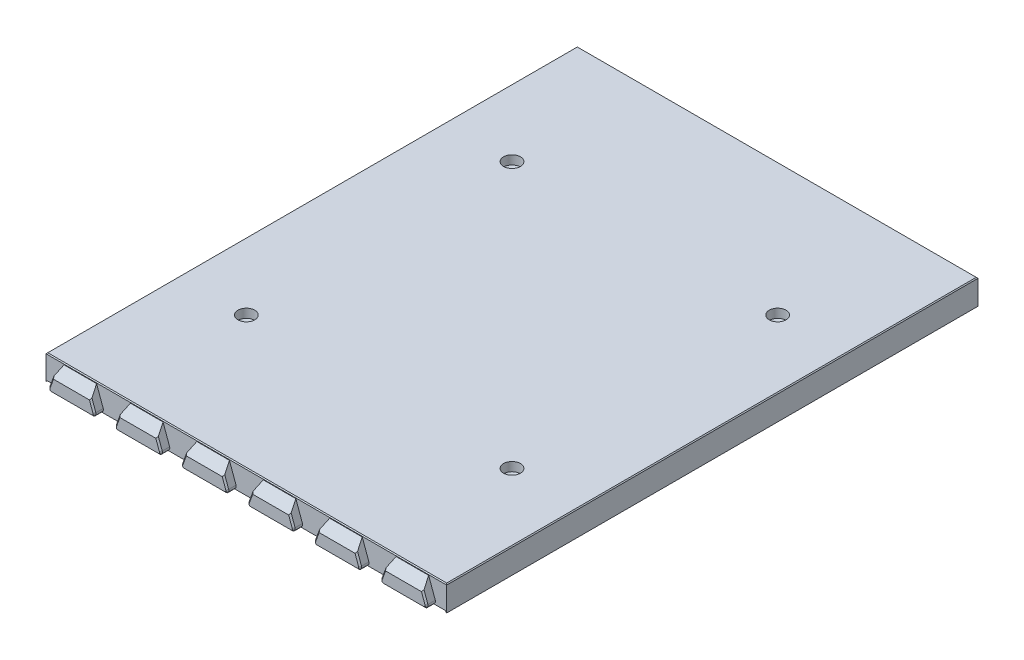
SolidWorks part; units mm, degrees
ref_plane "Front Plane" through (0, 0, 0) normal (0, 0, 1) x (1, 0, 0)
ref_plane "Top Plane" through (0, 0, 0) normal (0, 1, 0) x (1, 0, 0)
ref_plane "Right Plane" through (0, 0, 0) normal (1, 0, 0) x (0, 0, -1)
sketch "Sketch1" plane through (0, 0, 0) normal (0, 0, 1) x (1, 0, 0)
  line L0 (0, 0) -> (0, 8) construction
  line L1 (-67.875, 0) -> (0, 0) construction
  line L2 (-67.875, 0) -> (-67.875, 8)
  line L3 (-67.875, 8) -> (67.875, 8)
  line L5 (-67.875, 0) -> (-65.875, 0)
  line L6 (-65.875, 0) -> (-65.875, 6)
  line L7 (-65.875, 6) -> (65.875, 6)
  line L9 (65.875, 0) -> (65.875, 6)
  line L10 (67.875, 0) -> (65.875, 0)
  line L11 (67.875, 0) -> (67.875, 8)
  point P8 (0, 6)
  dimension "D2" = 6
  dimension "D1" = 67.875
  dimension "D3" = 2
  dimension "D4" = 2
extrude "Boss-Extrude1" add sketch "Sketch1" against normal blind 90
sketch "Sketch7" plane through (0, 0, 0) normal (0, 0, 1) x (1, 0, 0)
  line L2 (-65.875, 0) -> (65.875, 0)
  line L13 (-65.875, 0) -> (-65.875, 6)
  line L15 (-65.875, 6) -> (65.875, 6)
  line L16 (65.875, 0) -> (65.875, 6)
  line M3 (-65.875, 0) -> (-65.875, 6)
  line M4 (-65.875, 6) -> (65.875, 6)
  line M5 (65.875, 6) -> (65.875, 0)
extrude "Boss-Extrude7" add sketch "Sketch7" against normal blind 1 contours M4 M3 | M5 region at (0, 3, 0)
sketch "Sketch2" plane through (0, 0, 0) normal (0, 0, 1) x (1, 0, 0)
  line L14 (50.9118, 8) -> (48, 0)
  line L15 (67.875, 8) -> (-67.875, 8) construction
  line L16 (-67.875, 0) -> (67.875, 0) construction
  line L17 (48, 0) -> (64.5, 0)
  line L18 (50.9118, 8) -> (61.5882, 8)
  line L19 (-67.875, 0) -> (67.875, 0) construction
  line L21 (61.5882, 8) -> (64.5, 0)
  line L24 (45, 0) -> (45, 8) construction
  line L27 (28.4118, 8) -> (25.5, 0)
  line L28 (28.4118, 8) -> (39.0882, 8)
  line L29 (25.5, 0) -> (42, 0)
  line L30 (39.0882, 8) -> (42, 0)
  line L31 (5.9118, 8) -> (3, 0)
  line L32 (5.9118, 8) -> (16.5882, 8)
  line L33 (3, 0) -> (19.5, 0)
  line L34 (16.5882, 8) -> (19.5, 0)
  line L35 (-16.5882, 8) -> (-19.5, 0)
  line L36 (-16.5882, 8) -> (-5.9118, 8)
  line L37 (-19.5, 0) -> (-3, 0)
  line L38 (-5.9118, 8) -> (-3, 0)
  line L39 (50.9118, 8) -> (28.4118, 8) construction
  line L40 (67.5, 8) -> (67.5, 0) construction
  line L41 (67.875, 0) -> (67.875, 8) construction
  line L42 (-67.5, 8) -> (-67.5, 0) construction
  line L43 (-67.875, 8) -> (-67.875, 0) construction
  line L44 (-39.0882, 8) -> (-42, 0)
  line L45 (-39.0882, 8) -> (-28.4118, 8)
  line L46 (-42, 0) -> (-25.5, 0)
  line L47 (-28.4118, 8) -> (-25.5, 0)
  line L48 (-61.5882, 8) -> (-64.5, 0)
  line L49 (-61.5882, 8) -> (-50.9118, 8)
  line L50 (-64.5, 0) -> (-48, 0)
  line L51 (-50.9118, 8) -> (-48, 0)
  point P22 (56.25, 8)
  point P23 (33.75, 8)
  dimension "D1" = 70
  dimension "D2" = 0.375
  dimension "D3" = 3
  dimension "D4" = 3
  dimension "D5" = 70
  dimension "D7" = 22.5
  dimension "D8" = 22.5
  dimension "D9" = 0.375
  dimension "D10" = 48
  dimension "D11" = 8
  dimension "D6" = 6
extrude "Boss-Extrude4" add sketch "Sketch2" along normal blind 3
sketch "Sketch8" plane through (0, 0, 0) normal (0, -1, 0) x (1, 0, 0)
  line L0 (-67.875, -22.5) -> (67.875, -22.5) construction
  line L1 (-66.35, -20.2583) -> (-62.65, -21.605)
  line L2 (67.875, -90) -> (67.875, 0) construction
  line L3 (-67.875, 0) -> (-64.5, 0) construction
  line L4 (-66.5, -24.9559) -> (-66.5, -20.0441) construction
  line L5 (-66.5, -20.0441) -> (-62.5, -21.5) construction
  line L6 (-62.5, -21.5) -> (-62.5, -23.5) construction
  line L7 (-66.5, -90) -> (-66.5, -87.5441) construction
  line L8 (-66.5, -87.5441) -> (-62.5, -89) construction
  line L9 (-62.5, -89) -> (-62.5, -90) construction
  line L10 (-65.875, -90) -> (65.875, -90) construction
  line L11 (-62.5, -90) -> (-66.5, -90) construction
  line L12 (-66.5, -24.9559) -> (-62.5, -23.5) construction
  line L13 (0, -90) -> (0, 0) construction
  line L22 (-62.65, -21.605) -> (-62.65, -23.395)
  line L23 (-67.875, -90) -> (-67.875, 0) construction
  line L28 (-67.875, -90) -> (-65.875, -90) construction
  line L33 (-66.35, -24.7417) -> (-62.65, -23.395)
  line L34 (-66.35, -24.7417) -> (-66.35, -20.2583)
  line L35 (-66.35, -89.85) -> (-66.35, -87.7583)
  line L36 (-66.35, -87.7583) -> (-62.65, -89.105)
  line L37 (-62.65, -89.105) -> (-62.65, -89.85)
  line L38 (-62.65, -89.85) -> (-66.35, -89.85) construction
  line L39 (-66.35, -89.85) -> (-66.35, -90)
  line L40 (-66.35, -90) -> (-62.65, -90)
  line L41 (-62.65, -90) -> (-62.65, -89.85)
  line L42 (66.35, -90) -> (62.65, -90)
  line L43 (66.35, -89.85) -> (66.35, -90)
  line L44 (66.35, -89.85) -> (66.35, -87.7583)
  line L45 (66.35, -87.7583) -> (62.65, -89.105)
  line L46 (62.65, -89.105) -> (62.65, -89.85)
  line L47 (62.65, -90) -> (62.65, -89.85)
  line L48 (66.35, -24.7417) -> (66.35, -20.2583)
  line L49 (66.35, -24.7417) -> (62.65, -23.395)
  line L50 (62.65, -21.605) -> (62.65, -23.395)
  line L51 (66.35, -20.2583) -> (62.65, -21.605)
  point P19 (-62.5, -22.5)
  dimension "D1" = 22.5
  dimension "D2" = 0.15
  dimension "D3" = 70
  dimension "D4" = 4
  dimension "D5" = 1.375
  dimension "D6" = 4
  dimension "D7" = 70
  dimension "D8" = 1
  dimension "D9" = 1
  dimension "D10" = 0.15
extrude "Boss-Extrude8" add sketch "Sketch8" against normal up to next and the other way blind 2
chamfer "Chamfer4" distance 0.5 angle 45 14 edges at (-62.65, -2, -89.5525) (62.65, -2, -22.5) (64.5, -2, -20.9317) (66.35, -2, -22.5) (64.5, -2, -24.0683) (-64.5, -2, -20.9317) (-62.65, -2, -22.5) (-64.5, -2, -24.0683) (-66.35, -2, -22.5) (-66.35, -2, -88.8792) (-64.5, -2, -88.4317) (62.65, -2, -89.5525) (64.5, -2, -88.4317) (66.35, -2, -88.8792)
fillet "Fillet4" radius 1 12 edges at (64.5, 0, 1.5) (48, 0, 1.5) (42, 0, 1.5) (25.5, 0, 1.5) (19.5, 0, 1.5) (3, 0, 1.5) (-3, 0, 1.5) (-19.5, 0, 1.5) (-25.5, 0, 1.5) (-42, 0, 1.5) (-48, 0, 1.5) (-64.5, 0, 1.5)
chamfer "Chamfer6" distance 0.5 angle 45 30 edges at (49.7001, 4.671, 3) (62.7999, 4.671, 3) (56.25, 0, 3) (-17.7999, 4.671, 3) (-11.25, 0, 3) (-4.7001, 4.671, 3) (4.7001, 4.671, 3) (11.25, 0, 3) (17.7999, 4.671, 3) (27.2001, 4.671, 3) (40.2999, 4.671, 3) (33.75, 0, 3) (-40.2999, 4.671, 3) (-33.75, 0, 3) (-27.2001, 4.671, 3) (-62.7999, 4.671, 3) (-49.7001, 4.671, 3) (-56.25, 0, 3) (-63.891, 0.4264, 3) (-48.609, 0.4264, 3) (-41.391, 0.4264, 3) (-26.109, 0.4264, 3) (-18.891, 0.4264, 3) (-3.609, 0.4264, 3) (3.609, 0.4264, 3) (18.891, 0.4264, 3) (26.109, 0.4264, 3) (41.391, 0.4264, 3) (48.609, 0.4264, 3) (63.891, 0.4264, 3)
fillet "Fillet2" radius 2 23 edges at (0, 6, -1) (-65.875, 3, -1) (65.875, 6, -10.7156) (65.875, 3, -1) (-65.875, 6, -10.7156) (-62.65, 6, -89.5525) (62.65, 6, -89.5525) (65.875, 3, -87.9312) (64.2625, 6, -88.5181) (64.2625, 6, -21.0181) (65.875, 3, -20.4312) (62.65, 6, -22.5) (64.2625, 6, -23.9819) (65.875, 3, -24.5688) (65.875, 6, -56.25) (-65.875, 3, -24.5688) (-64.2625, 6, -23.9819) (-65.875, 3, -87.9312) (-64.2625, 6, -88.5181) (-65.875, 6, -56.25) (-62.65, 6, -22.5) (-65.875, 3, -20.4312) (-64.2625, 6, -21.0181)
mirror "Mirror2" about plane through (0, 0, -90) normal (0, 0, 1) of "Fillet4", "Boss-Extrude1", "Boss-Extrude7", "Boss-Extrude4", "Boss-Extrude8", "Chamfer4", "Fillet2", "Chamfer6"
sketch "Sketch9" plane through (0, 0, 0) normal (0, 1, 0) x (1, 0, 0)
  line L16 (0, 90) -> (0, 0) construction
  line L17 (-67.875, 90) -> (67.875, 90) construction
  line L20 (-67.875, 180) -> (-67.875, 0) construction
  line L25 (67.875, 180) -> (67.875, 0) construction
  circle A0 centre (-45, 45) radius 5
  circle A4 centre (45, 45) radius 5
  circle A5 centre (45, 135) radius 5
  circle A6 centre (-45, 135) radius 5
  point P23 (0, 90)
  point P24 (0, 90)
  dimension "D3" = 10
  dimension "D1" = 45
  dimension "D2" = 45
extrude "Boss-Extrude9" add sketch "Sketch9" along normal up to next
fillet "Fillet3" radius 3 4 edges at (-45, 6, -50) (45, 6, -50) (-45, 6, -140) (45, 6, -140)
sketch "Sketch10" plane through (0, 0, 0) normal (0, 1, 0) x (1, 0, 0)
  circle A0 centre (-45, 135) radius 1.85
  circle A1 centre (-45, 45) radius 1.85
  circle A2 centre (45, 45) radius 1.85
  circle A3 centre (45, 135) radius 1.85
  dimension "D1" = 3.7
extrude "Cut-Extrude2" cut sketch "Sketch10" along normal through all
sketch "Sketch11" plane through (0, 8, 0) normal (0, 1, 0) x (1, 0, 0)
  circle A0 centre (-45, 135) radius 2.85
  circle A1 centre (45, 135) radius 2.85
  circle A2 centre (45, 45) radius 2.85
  circle A3 centre (-45, 45) radius 2.85
  dimension "D1" = 5.7
extrude "Cut-Extrude3" cut sketch "Sketch11" against normal blind 3
chamfer "Chamfer7" distance 1 angle 45 4 edges at (45, 5, -133.15) (-45, 5, -133.15) (45, 5, -43.15) (-45, 5, -43.15)
sketch "Sketch12" plane through (0, 0, 0) normal (1, 0, 0) x (0, 0, -1)
  line L0 (0, 7.5) -> (-3, 4.5)
  line L1 (-3, 1.171) -> (-3, 8) construction
  line L2 (-3, 4.5) -> (-3, 7.5)
  line L3 (-3, 7.5) -> (0, 7.5) construction
  line L4 (90, 8) -> (90, 0) construction
  line L5 (180, 8) -> (0, 8) construction
  line L6 (180, 0) -> (0, 0) construction
  line L8 (183, 4.5) -> (183, 7.5)
  line L9 (180, 7.5) -> (183, 4.5)
  line L10 (0, 0) -> (0, 8) construction
  line L11 (-3, 8) -> (-2.5, 8) construction
  line L12 (-3, 7.5) -> (-3, 8)
  line L13 (-3, 8) -> (0, 8)
  line L14 (0, 8) -> (0, 7.5)
  line L15 (183, 7.5) -> (180, 7.5) construction
  line L16 (180, 8) -> (180, 7.5)
  line L17 (183, 8) -> (180, 8)
  line L18 (183, 7.5) -> (183, 8)
  dimension "D1" = 45
  dimension "D2" = 3
  dimension "D3" = 0.5
extrude "Cut-Extrude4" cut sketch "Sketch12" against normal through all both and the other way through all
sketch "Sketch13" plane through (0, 0, -180) normal (0, 0, -1) x (-1, 0, 0)
  line L0 (-67.375, 0) -> (-67.875, -0.5)
  line L1 (-63.0719, 0) -> (-67.875, 0) construction
  line L2 (-67.875, -0.5) -> (-67.875, 0)
  line L3 (-67.875, 0) -> (-67.375, 0)
  line L4 (0, 0) -> (0, 8) construction
  line L5 (-67.875, 8) -> (67.875, 8) construction
  line L6 (67.875, 0) -> (67.375, 0)
  line L7 (67.875, -0.5) -> (67.875, 0)
  line L8 (67.375, 0) -> (67.875, -0.5)
  dimension "D1" = 0.5
  dimension "D2" = 0.5
extrude "Boss-Extrude10" add sketch "Sketch13" against normal up to surface (180 mm away) up to face at (0, 2.9792, 0)
chamfer "Chamfer8" distance 0.3 angle 45 4 edges at (-67.875, 8, -90) (67.875, 8, -90) (0, 8, -180) (0, 8, 0)
